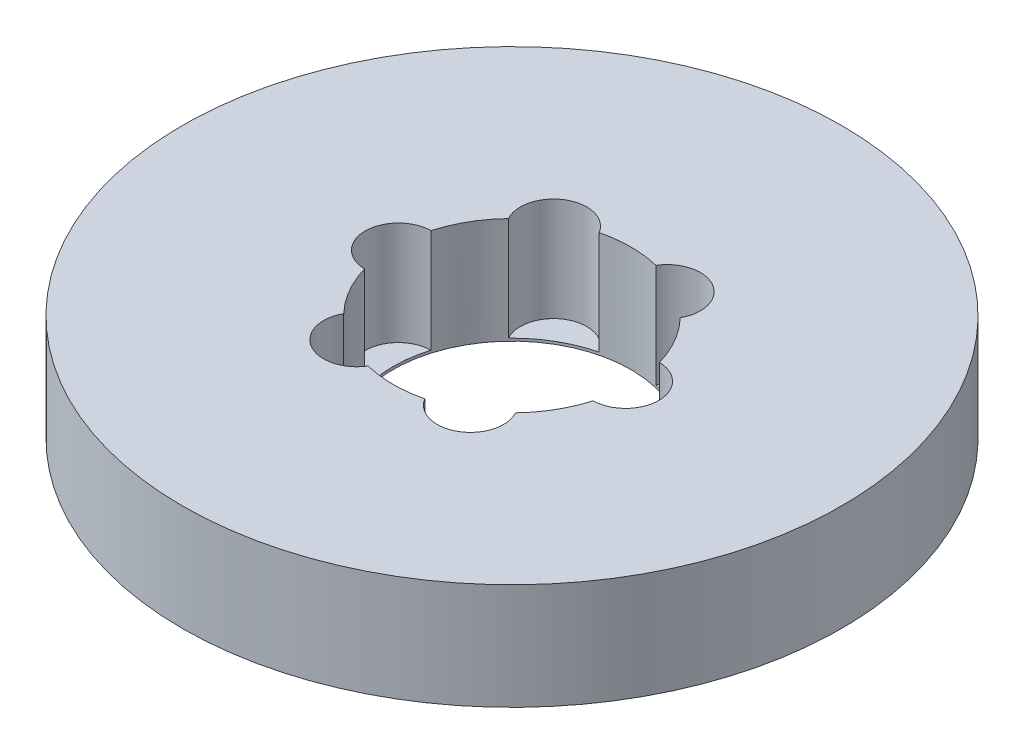
SolidWorks part; units mm, degrees
ref_plane "Front Plane" through (0, 0, 0) normal (0, 0, 1) x (1, 0, 0)
ref_plane "Top Plane" through (0, 0, 0) normal (0, 1, 0) x (1, 0, 0)
ref_plane "Right Plane" through (0, 0, 0) normal (1, 0, 0) x (0, 0, -1)
sketch "Sketch1" plane through (0, 0, 0) normal (0, 1, 0) x (1, 0, 0)
  circle A0 centre (0, 0) radius 90
  dimension "FLANGE_OD" = 180
extrude "Boss-Extrude1" add sketch "Sketch1" along normal blind 29
sketch "Sketch2" plane through (0, 0, 0) normal (0, 1, 0) x (1, 0, 0)
  circle A0 centre (0, 0) radius 32.5
  dimension "BORE_D" = 65
extrude "Cut-Extrude1" cut sketch "Sketch2" along normal through all
sketch "Sketch3" plane through (0, 29, 0) normal (0, 1, 0) x (1, 0, 0)
  circle A0 centre (0, 0) radius 31.0226 construction
  circle A1 centre (-31.0226, 0) radius 9.0727
  dimension "BOLT_D" = 18.1454
  dimension "BOLT_PCD" = 62.0453
extrude "Cut-Extrude2" cut sketch "Sketch3" against normal blind 28.284
pattern_circular "CirPattern1" count 6 over 360 about axis through (0, 0, 0) along (0, 1, 0) of "Cut-Extrude2"
